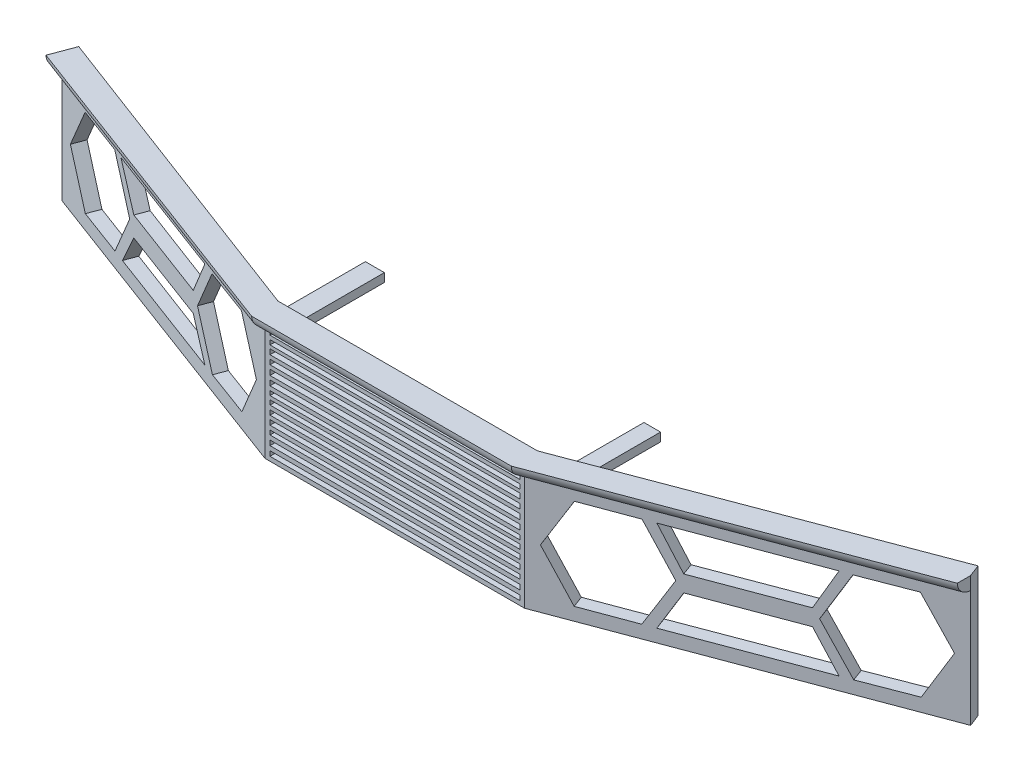
SolidWorks part; units mm, degrees
ref_plane "Front Plane" through (0, 0, 0) normal (0, 0, 1) x (1, 0, 0)
ref_plane "Top Plane" through (0, 0, 0) normal (0, 1, 0) x (1, 0, 0)
ref_plane "Right Plane" through (0, 0, 0) normal (1, 0, 0) x (0, 0, -1)
sketch "Sketch1" plane through (0, 0, 0) normal (0, 1, 0) x (1, 0, 0)
  line L0 (0, 0) -> (50.8, 0)
  line L1 (50.8, 2.54) -> (0, 2.54)
  line L2 (114.3, 23.7902) -> (113.3788, 26.1573)
  line L3 (50.8, 2.54) -> (113.3788, 26.1573)
  line L4 (50.8, 0) -> (114.3, 23.7902)
  line L5 (0, 0) -> (-63.5, 23.7902)
  line L6 (-63.5, 23.7902) -> (-62.6089, 26.1688)
  line L7 (-62.6089, 26.1688) -> (0, 2.54)
  dimension "D1" = 50.8
  dimension "D2" = 2.54
  dimension "D3" = 2.54
  dimension "D4" = 63.5
  dimension "D5" = 63.5
  dimension "D6" = 2.54
extrude "Boss-Extrude1" add sketch "Sketch1" along normal blind 25.4
sketch "Sketch3" plane through (0, 25.4, 0) normal (0, 1, 0) x (1, 0, 0)
  line L0 (-63.5, 23.7902) -> (0, 0)
  line L1 (0, 0) -> (50.8, 0)
  line L2 (50.8, 0) -> (114.3, 23.7902)
  line L3 (114.3, 23.7902) -> (114.3, 21.1847)
  line L4 (114.3, 21.1847) -> (50.8, -2.6055)
  line L5 (50.8, -2.6055) -> (0, -2.6055)
  line L6 (0, -2.6055) -> (-64.356, 21.5054)
  line L7 (-64.356, 21.5054) -> (-63.5, 23.7902)
extrude "Boss-Extrude2" add sketch "Sketch3" against normal blind 2.54
fillet "Fillet1" radius 2.54 3 edges at (-32.178, 22.86, -9.45) (25.4, 22.86, 2.6055) (82.55, 22.86, -9.2896)
sketch "Sketch4" plane through (0, 0, 0) normal (0, 0, 1) x (1, 0, 0)
  line L1 (49.8771, 0.8427) -> (0.9846, 0.8427)
  line L2 (49.8771, 0.8427) -> (49.8771, 1.7964)
  line L3 (49.8771, 1.7964) -> (0.9846, 1.7964)
  line L4 (0.9846, 0.8427) -> (0.9846, 1.7964)
  line L5 (49.8771, 2.6498) -> (0.9846, 2.6498)
  line L6 (49.8771, 2.6498) -> (49.8771, 3.6035)
  line L7 (49.8771, 3.6035) -> (0.9846, 3.6035)
  line L8 (0.9846, 2.6498) -> (0.9846, 3.6035)
  line L9 (49.8771, 4.4569) -> (0.9846, 4.4569)
  line L10 (49.8771, 4.4569) -> (49.8771, 5.3103)
  line L11 (49.8771, 5.3103) -> (0.9846, 5.3103)
  line L12 (0.9846, 4.4569) -> (0.9846, 5.3103)
  line L13 (49.8771, 6.1134) -> (0.9846, 6.1134)
  line L14 (49.8771, 6.1134) -> (49.8771, 7.0672)
  line L15 (49.8771, 7.0672) -> (0.9846, 7.0672)
  line L16 (0.9846, 6.1134) -> (0.9846, 7.0672)
  line L17 (49.8771, 7.8201) -> (0.9846, 7.8201)
  line L18 (49.8771, 7.8201) -> (49.8771, 8.7237)
  line L19 (49.8771, 8.7237) -> (0.9846, 8.7237)
  line L20 (0.9846, 7.8201) -> (0.9846, 8.7237)
  line L21 (49.8771, 9.5269) -> (0.9846, 9.5269)
  line L22 (49.8771, 9.5269) -> (49.8771, 10.4304)
  line L23 (49.8771, 10.4304) -> (0.9846, 10.4304)
  line L24 (0.9846, 9.5269) -> (0.9846, 10.4304)
  line L25 (49.8771, 11.1332) -> (0.9846, 11.1332)
  line L26 (49.8771, 11.1332) -> (49.8771, 11.9865)
  line L27 (49.8771, 11.9865) -> (0.9846, 11.9865)
  line L28 (0.9846, 11.1332) -> (0.9846, 11.9865)
  line L29 (49.8771, 12.7897) -> (0.9846, 12.7897)
  line L30 (49.8771, 12.7897) -> (49.8771, 13.7937)
  line L31 (49.8771, 13.7937) -> (0.9846, 13.7937)
  line L32 (0.9846, 12.7897) -> (0.9846, 13.7937)
  line L33 (49.8771, 14.5466) -> (0.9846, 14.5466)
  line L34 (49.8771, 14.5466) -> (49.8771, 15.6008)
  line L35 (49.8771, 15.6008) -> (0.9846, 15.6008)
  line L36 (0.9846, 14.5466) -> (0.9846, 15.6008)
  line L37 (49.8771, 16.3537) -> (0.9846, 16.3537)
  line L38 (49.8771, 16.3537) -> (49.8771, 17.3075)
  line L39 (49.8771, 17.3075) -> (0.9846, 17.3075)
  line L40 (0.9846, 16.3537) -> (0.9846, 17.3075)
  line L41 (49.8771, 18.0605) -> (0.9846, 18.0605)
  line L42 (49.8771, 18.0605) -> (49.8771, 19.0644)
  line L43 (49.8771, 19.0644) -> (0.9846, 19.0644)
  line L44 (0.9846, 18.0605) -> (0.9846, 19.0644)
  line L45 (49.8771, 19.717) -> (0.9846, 19.717)
  line L46 (49.8771, 19.717) -> (49.8771, 20.6205)
  line L47 (49.8771, 20.6205) -> (0.9846, 20.6205)
  line L48 (0.9846, 19.717) -> (0.9846, 20.6205)
  line L49 (49.8771, 21.3735) -> (0.9846, 21.3735)
  line L50 (49.8771, 21.3735) -> (49.8771, 22.2269)
  line L51 (49.8771, 22.2269) -> (0.9846, 22.2269)
  line L52 (0.9846, 21.3735) -> (0.9846, 22.2269)
extrude "Cut-Extrude1" cut sketch "Sketch4" against normal blind 4.572
sketch "Sketch5" plane through (6.2527, 0, 16.6896) normal (0.3508, 0, 0.9364) x (0.9364, 0, -0.3508)
  line L0 (115.3812, 11.431) -> (47.571, 11.431) construction
  line L1 (115.3812, 22.862) -> (115.3812, 0) construction
  line L2 (47.571, 22.862) -> (47.571, 0) construction
  line L3 (95.3855, 2.5133) -> (91.3422, 9.6871)
  line L4 (107.8723, 2.5869) -> (112.936, 11.5046)
  line L5 (112.936, 11.5046) -> (107.7449, 20.3487)
  line L6 (107.7449, 20.3487) -> (97.4901, 20.2751)
  line L7 (97.4901, 20.2751) -> (92.4265, 11.3574)
  line L8 (92.4265, 11.3574) -> (97.6176, 2.5133)
  line L9 (97.6176, 2.5133) -> (107.8723, 2.5869)
  line L10 (65.3963, 2.5133) -> (70.5566, 11.4108)
  line L11 (70.5566, 11.4108) -> (65.4313, 20.3285)
  line L12 (65.4313, 20.3285) -> (55.1457, 20.3487)
  line L13 (55.1457, 20.3487) -> (49.9854, 11.4512)
  line L14 (49.9854, 11.4512) -> (55.1107, 2.5335)
  line L15 (55.1107, 2.5335) -> (65.3963, 2.5133)
  line L16 (91.3422, 9.6871) -> (71.7718, 9.6871)
  line L17 (71.7718, 9.6871) -> (67.6818, 2.5133)
  line L18 (67.6818, 2.5133) -> (95.3855, 2.5133)
  line L19 (91.3422, 12.8951) -> (71.7718, 12.8951)
  line L20 (71.7718, 12.8951) -> (67.6818, 20.3285)
  line L21 (67.6818, 20.3285) -> (95.3855, 20.3285)
  line L22 (95.3855, 20.3285) -> (91.3422, 12.8951)
  circle A0 centre (102.6812, 11.431) radius 8.8811 construction
  circle A1 centre (60.271, 11.431) radius 8.9076 construction
  dimension "D1" = 12.7
  dimension "D2" = 12.7
extrude "Cut-Extrude2" cut sketch "Sketch5" against normal blind 4.572
sketch "Sketch6" plane through (0, 0, 0) normal (-0.3508, 0, 0.9364) x (0.9364, 0, 0.3508)
  line L0 (0, 11.431) -> (-67.8102, 11.431) construction
  line L1 (0, 22.862) -> (0, 0) construction
  line L2 (-67.8102, 22.862) -> (-67.8102, 0) construction
  line L3 (-20.0814, 2.8719) -> (-47.6392, 2.8719)
  line L4 (-7.7147, 2.9477) -> (-2.8606, 11.5067)
  line L5 (-2.8606, 11.5067) -> (-7.8459, 19.9901)
  line L6 (-7.8459, 19.9901) -> (-17.6853, 19.9143)
  line L7 (-17.6853, 19.9143) -> (-22.5394, 11.3552)
  line L8 (-22.5394, 11.3552) -> (-17.5541, 2.8719)
  line L9 (-17.5541, 2.8719) -> (-7.7147, 2.9477)
  line L10 (-50.1255, 2.8719) -> (-45.2055, 11.4683)
  line L11 (-45.2055, 11.4683) -> (-50.1902, 20.0274)
  line L12 (-50.1902, 20.0274) -> (-60.0949, 19.9901)
  line L13 (-60.0949, 19.9901) -> (-65.0149, 11.3936)
  line L14 (-65.0149, 11.3936) -> (-60.0302, 2.8346)
  line L15 (-60.0302, 2.8346) -> (-50.1255, 2.8719)
  line L16 (-47.6392, 2.8719) -> (-43.822, 9.1517)
  line L17 (-20.0814, 2.8719) -> (-23.9656, 9.1517)
  line L18 (-23.9656, 9.1517) -> (-43.822, 9.1517)
  line L19 (-23.9656, 13.0426) -> (-43.822, 13.0426)
  line L20 (-43.822, 13.0426) -> (-48.1423, 20.0274)
  line L21 (-48.1423, 20.0274) -> (-20.0814, 20.0274)
  line L22 (-20.0814, 20.0274) -> (-23.9656, 13.0426)
  circle A0 centre (-12.7, 11.431) radius 8.5214 construction
  circle A1 centre (-55.1102, 11.431) radius 8.5778 construction
  dimension "D1" = 12.7
  dimension "D2" = 12.7
extrude "Cut-Extrude3" cut sketch "Sketch6" against normal blind 4.572
sketch "Sketch7" plane through (0, 0, -2.54) normal (0, 0, -1) x (-1, 0, 0)
  line L0 (-50.8, 25.4) -> (-50.8, 0) construction
  line L1 (-50.8, 18.126) -> (-54.0443, 18.126)
  line L2 (-50.8, 18.126) -> (-50.8, 19.8019)
  line L3 (-50.8, 19.8019) -> (-54.0443, 19.8019)
  line L4 (-54.0443, 18.126) -> (-54.0443, 19.8019)
  line L5 (-50.8, 18.126) -> (3.7185, 18.126) construction
  line L6 (0, 25.4) -> (0, 0) construction
  line L7 (0, 18.126) -> (3.7185, 18.126)
  line L8 (0, 18.126) -> (0, 19.8019)
  line L9 (0, 19.8019) -> (3.7185, 19.8019)
  line L10 (3.7185, 18.126) -> (3.7185, 19.8019)
extrude "Boss-Extrude3" add sketch "Sketch7" along normal blind 20.828
